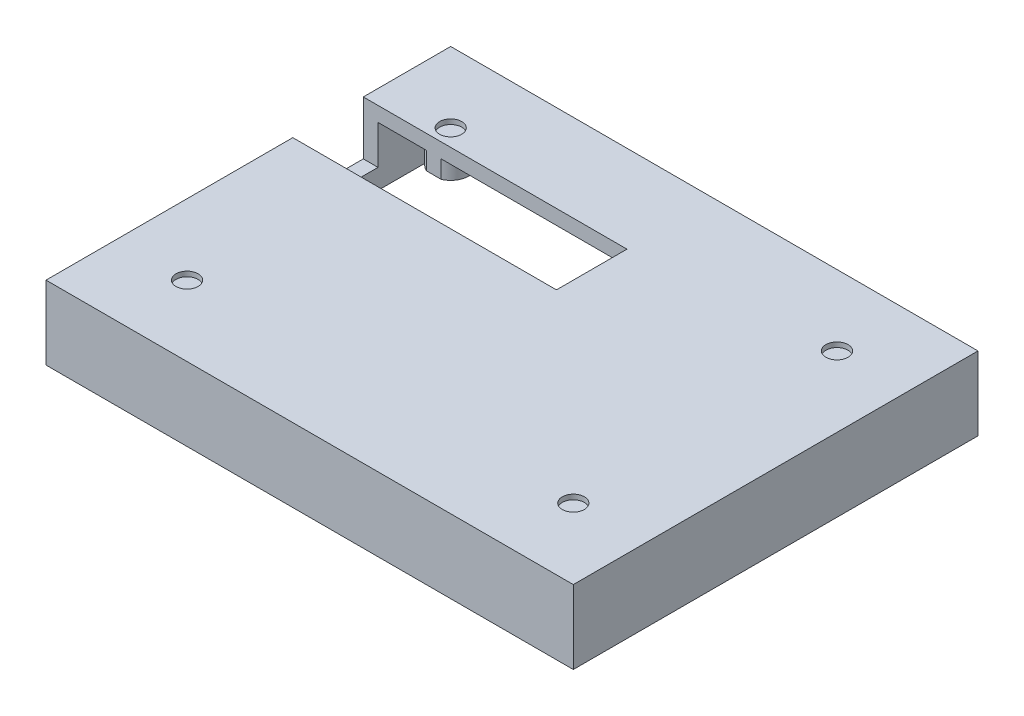
SolidWorks part; units mm, degrees
ref_plane "Front Plane" through (0, 0, 0) normal (0, 0, 1) x (1, 0, 0)
ref_plane "Top Plane" through (0, 0, 0) normal (0, 1, 0) x (1, 0, 0)
ref_plane "Right Plane" through (0, 0, 0) normal (1, 0, 0) x (0, 0, -1)
sketch "Sketch1" plane through (0, 0, 0) normal (0, 1, 0) x (1, 0, 0)
  line L1 (-43, -33) -> (43, -33)
  line L2 (-43, -33) -> (-43, 33)
  line L3 (-43, 33) -> (43, 33)
  line L4 (43, -33) -> (43, 33)
  line L5 (-43, -33) -> (43, 33) construction
  line L6 (-43, 33) -> (43, -33) construction
  point P0 (0, 0)
extrude "Boss-Extrude1" add sketch "Sketch1" along normal blind 12
sketch "Sketch2" plane through (0, 0, 0) normal (0, -1, 0) x (1, 0, 0)
  line L1 (-40.6, -30.6) -> (40.6, -30.6)
  line L2 (-40.6, -30.6) -> (-40.6, 30.6)
  line L3 (-40.6, 30.6) -> (40.6, 30.6)
  line L4 (40.6, -30.6) -> (40.6, 30.6)
  line L5 (-40.6, -30.6) -> (40.6, 30.6) construction
  line L6 (-40.6, 30.6) -> (40.6, -30.6) construction
  point P0 (0, 0)
extrude "Cut-Extrude1" cut sketch "Sketch2" against normal blind 9.6
sketch "Sketch3" plane through (0, 9.6, 0) normal (0, -1, 0) x (1, 0, 0)
  line L1 (-26, -18) -> (26, -18)
  line L2 (-26, -18) -> (-26, 18)
  line L3 (-26, 18) -> (26, 18)
  line L4 (26, -18) -> (26, 18)
  line L5 (-26, -18) -> (26, 18) construction
  line L6 (-26, 18) -> (26, -18) construction
  point P0 (0, 0)
extrude "Cut-Extrude2" cut sketch "Sketch3" against normal blind 1.6
sketch "Sketch4" plane through (0, 11.2, 0) normal (0, -1, 0) x (1, 0, 0)
  circle A0 centre (-31.5, -21.5) radius 3
  circle A1 centre (31.5, -21.5) radius 3
  circle A2 centre (-31.5, 21.5) radius 3
  circle A3 centre (31.5, 21.5) radius 3
extrude "Boss-Extrude2" add sketch "Sketch4" along normal blind 4.5
sketch "Sketch5" plane through (0, 11.2, 0) normal (0, -1, 0) x (1, 0, 0)
  circle A0 centre (-31.5, -21.5) radius 1.8
  circle A1 centre (31.5, -21.5) radius 1.8
  circle A2 centre (-31.5, 21.5) radius 1.8
  circle A3 centre (31.5, 21.5) radius 1.8
extrude "Cut-Extrude3" cut sketch "Sketch5" against normal blind 4.5
sketch "Sketch6" plane through (0, 0, 0) normal (1, 0, 0) x (0, 0, -1)
  line L1 (7.25, 3.25) -> (18.75, 3.25)
  line L2 (7.25, 3.25) -> (7.25, 12.75)
  line L3 (7.25, 12.75) -> (18.75, 12.75)
  line L4 (18.75, 3.25) -> (18.75, 12.75)
  line L5 (7.25, 3.25) -> (18.75, 12.75) construction
  line L6 (7.25, 12.75) -> (18.75, 3.25) construction
  circle A0 centre (-5, 8) radius 1.25
  point P0 (13, 8)
extrude "Cut-Extrude4" cut sketch "Sketch6" against normal blind 50
